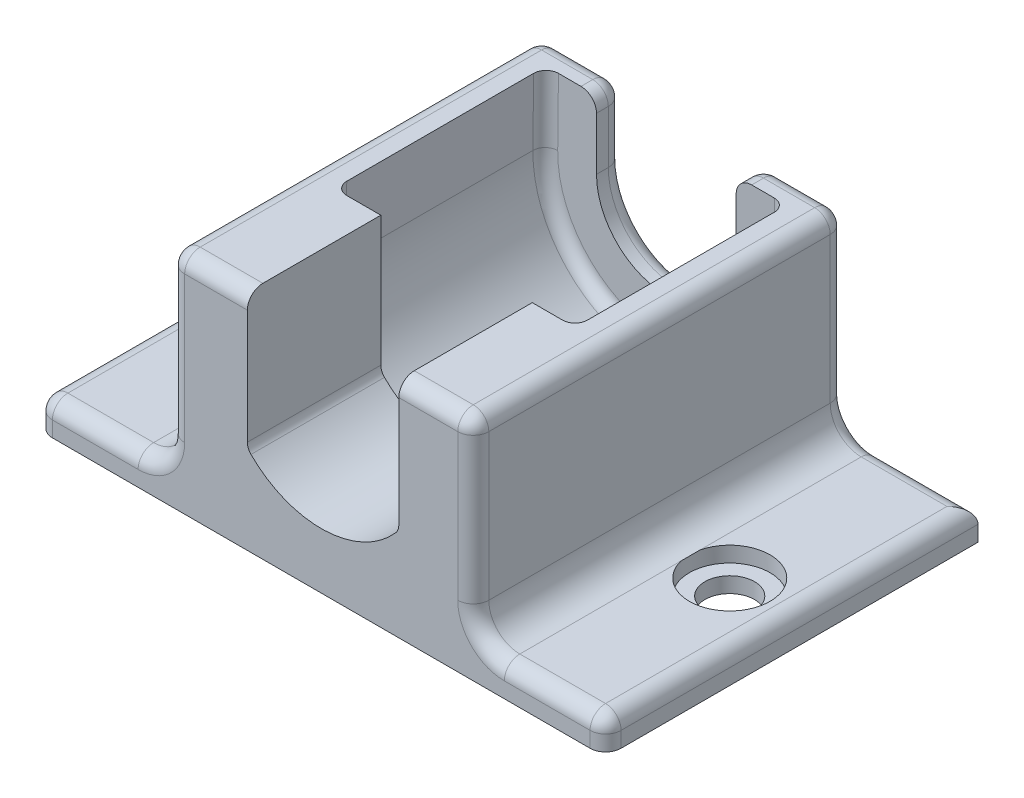
SolidWorks part; units mm, degrees
ref_plane "Front Plane" through (0, 0, 0) normal (0, 0, 1) x (1, 0, 0)
ref_plane "Top Plane" through (0, 0, 0) normal (0, 1, 0) x (1, 0, 0)
ref_plane "Right Plane" through (0, 0, 0) normal (1, 0, 0) x (0, 0, -1)
sketch "Sketch1" plane through (0, 0, 0) normal (0, 0, 1) x (1, 0, 0)
  line L6 (-23.375, 0) -> (-18.375, 0)
  line L7 (18.375, 0) -> (23.375, 0)
  arc A2 (-18.375, 0) -> (18.375, 0) centre (0, 0) ccw
  arc A3 (-23.375, 0) -> (23.375, 0) centre (0, 0) ccw
  dimension "D1" = 18.375
  dimension "D2" = 23.375
extrude "Boss-Extrude1" add sketch "Sketch1" along normal blind 18.5 contours L6 A3 L7 A2
sketch "Sketch2" plane through (0, 0, 18.5) normal (0, 0, 1) x (1, 0, 0)
  line L0 (-16.375, 0) -> (-23.375, 0)
  line L1 (16.375, 0) -> (23.375, 0)
  arc A0 (-23.375, 0) -> (23.375, 0) centre (0, 0) ccw
  arc A1 (-16.375, 0) -> (16.375, 0) centre (0, 0) ccw
  dimension "D1" = 32.75
  dimension "D2" = 46.75
extrude "Boss-Extrude2" add sketch "Sketch2" along normal blind 18
sketch "Sketch3" plane through (0, 0, 0) normal (0, 0, -1) x (-1, 0, 0)
  line L0 (-23.375, 0) -> (23.375, 0)
  arc A0 (-23.375, 0) -> (23.375, 0) centre (0, 0) ccw
  circle A1 centre (0, -7) radius 6.5
  dimension "D2" = 13
  dimension "D1" = 7
extrude "Boss-Extrude3" add sketch "Sketch3" along normal blind 5
sketch "Sketch4" plane through (0, 0, 0) normal (0, 1, 0) x (1, 0, 0)
  line L0 (23.375, -36.5) -> (23.375, 5)
  line L1 (23.375, 5) -> (-23.375, 5)
  line L2 (-23.375, 5) -> (-23.375, -36.5)
  line L3 (-23.375, -36.5) -> (-16.375, -36.5)
  line L4 (-16.375, -36.5) -> (-16.375, -18.5)
  line L5 (-16.375, -18.5) -> (-18.375, -18.5)
  line L6 (-18.375, -18.5) -> (-18.375, 0)
  line L7 (-18.375, 0) -> (18.375, 0)
  line L8 (18.375, 0) -> (18.375, -18.5)
  line L9 (18.375, -18.5) -> (16.375, -18.5)
  line L10 (16.375, -18.5) -> (16.375, -36.5)
  line L11 (16.375, -36.5) -> (23.375, -36.5)
extrude "Boss-Extrude4" add sketch "Sketch4" along normal blind 5
sketch "Sketch5" plane through (0, 0, -5) normal (0, 0, -1) x (-1, 0, 0)
  line L0 (-6.5, -7) -> (-6.5, 5)
  line L1 (-23.375, 5) -> (23.375, 5) construction
  line L2 (-6.5, 5) -> (6.5, 5)
  line L3 (6.5, 5) -> (6.5, -7)
  line L4 (-6.5, -7) -> (6.5, -7)
  circle A0 centre (0, -7) radius 6.5 construction
  circle A1 centre (0, -7) radius 6.5 construction
extrude "Cut-Extrude1" cut sketch "Sketch5" against normal blind 5
ref_plane "Plane1" through (0, -54, 0) normal (0, 1, 0) x (1, 0, 0)
sketch "Sketch6" plane through (0, -54, 0) normal (0, 1, 0) x (1, 0, 0)
  line L0 (23.375, -36.5) -> (23.375, 5) construction
  line L1 (13.215, 5) -> (23.375, 5)
  line L2 (13.215, 5) -> (13.215, -36.5)
  line L3 (13.215, -36.5) -> (23.375, -36.5)
  line L4 (23.375, 5) -> (23.375, -36.5)
  line L6 (-13.215, 5) -> (-23.375, 5)
  line L7 (-13.215, 5) -> (-13.215, -36.5)
  line L8 (-13.215, -36.5) -> (-23.375, -36.5)
  line L9 (-23.375, 5) -> (-23.375, -36.5)
  line L10 (-23.375, 5) -> (-23.375, -36.5) construction
  line L11 (-23.375, -36.5) -> (-16.375, -36.5) construction
  line L12 (16.375, -36.5) -> (23.375, -36.5) construction
  line L13 (-6.5, 5) -> (-23.375, 5) construction
  line L14 (23.375, 5) -> (6.5, 5) construction
  line L15 (6.5, 5) -> (-6.5, 5) construction
  line L16 (-3.175, 5) -> (3.175, 5)
  line L17 (-3.175, 5) -> (-3.175, -36.5)
  line L18 (-3.175, -36.5) -> (3.175, -36.5)
  line L19 (3.175, 5) -> (3.175, -36.5)
  line L20 (-16.375, -36.5) -> (16.375, -36.5) construction
  dimension "D1" = 6.35
  dimension "D2" = 3.175
  dimension "D3" = 10.16
  dimension "D4" = 0
  dimension "D5" = 10.16
  dimension "D7" = 0
extrude "Boss-Extrude5" add sketch "Sketch6" along normal up to next
sketch "Sketch7" plane through (0, -54, 0) normal (0, -1, 0) x (1, 0, 0)
  line L0 (-13.215, -5) -> (-23.375, -5) construction
  line L1 (-23.375, 36.5) -> (37.5, 36.5)
  line L2 (-23.375, 36.5) -> (-23.375, -5)
  line L3 (-23.375, -5) -> (37.5, -5)
  line L4 (37.5, 36.5) -> (37.5, -5)
  line L5 (-23.375, 36.5) -> (-13.215, 36.5) construction
  line L7 (-23.375, -5) -> (-23.375, 36.5) construction
  dimension "D1" = 0
  dimension "D2" = 0
  dimension "D4" = 37.5
extrude "Boss-Extrude6" add sketch "Sketch7" against normal blind 5
sketch "Sketch10" plane through (23.375, 0, 0) normal (1, 0, 0) x (0, 0, -1)
  line L0 (5, -49) -> (-36.5, -49) construction
  line L1 (-31.7375, -23.1584) -> (0.2375, -23.1584)
  line L2 (-31.7375, -23.1584) -> (-31.7375, -46)
  line L3 (-31.7375, -46) -> (0.2375, -46)
  line L4 (0.2375, -23.1584) -> (0.2375, -46)
  line L5 (5, 5) -> (5, -49) construction
  line L6 (-36.5, 5) -> (-36.5, -49) construction
  line L7 (-36.5, -23.1584) -> (5, -23.1584) construction
  dimension "D1" = 3
  dimension "D2" = 4.7625
  dimension "D3" = 4.7625
  dimension "D4" = 0
extrude "Cut-Extrude2" cut sketch "Sketch10" against normal through all
sketch "Sketch12" plane through (0, 0, -5) normal (0, 0, -1) x (-1, 0, 0)
  line L0 (-23.375, 0) -> (-23.375, 5)
  line L1 (-23.375, 5) -> (-12.2555, 5)
  line L2 (23.375, 5) -> (23.375, 0)
  line L3 (-12.2555, -7) -> (-12.2555, 5)
  line L4 (12.2555, -7) -> (12.2555, 5)
  line L5 (12.2555, 5) -> (23.375, 5)
  arc A0 (-23.375, 0) -> (23.375, 0) centre (0, 0) ccw
  arc A1 (-12.2555, -7) -> (12.2555, -7) centre (0, -7) ccw
  dimension "D1" = 24.511
extrude "Boss-Extrude7" add sketch "Sketch12" against normal through all contours A1 L4 L5 L2 A0 L0 L1 L3
sketch "Sketch13" plane through (0, 0, -5) normal (0, 0, -1) x (-1, 0, 0)
  line L1 (-12.3818, -6.8682) -> (-12.2555, 5)
  line L2 (-12.2555, 5) -> (12.2555, 5)
  line L3 (12.2555, 5) -> (12.3818, -6.8682)
  arc A0 (-12.3818, -6.8682) -> (12.3818, -6.8682) centre (0, -7) ccw
  dimension "D1" = 24.765
extrude "Cut-Extrude4" cut sketch "Sketch13" against normal through all
ref_plane "Plane2" through (0, 0, 19.4475) normal (0, 0, -1) x (-1, 0, 0)
sketch "Sketch14" plane through (0, 0, 19.4475) normal (0, 0, -1) x (-1, 0, 0)
  line L0 (-7.9375, -0.6579) -> (-7.9375, -13.3421)
  line L1 (7.5565, -13.7915) -> (7.5565, -1.1074)
  line L2 (-7.9375, -0.6579) -> (-7.9375, 5)
  line L3 (-7.9375, 5) -> (-23.375, 5)
  line L4 (-23.375, 5) -> (-23.375, 0)
  line L6 (7.5565, -1.1074) -> (7.5565, 5)
  line L7 (7.5565, 5) -> (23.375, 5)
  line L8 (23.375, 5) -> (23.375, 0)
  arc A0 (-7.9375, -13.3421) -> (7.5565, -13.7915) centre (0, -7) ccw
  arc A1 (-23.375, 0) -> (23.375, 0) centre (0, 0) ccw
  arc A2 (-12.3818, -6.8682) -> (12.3818, -6.8682) centre (0, -7) ccw construction
  dimension "D1" = 20.32
  dimension "D3" = 23.375
  dimension "D2" = 15.494
extrude "Boss-Extrude8" add sketch "Sketch14" against normal through all
sketch "Sketch15" plane through (0, 0, -5) normal (0, 0, -1) x (-1, 0, 0)
  line L0 (-6.0325, -7) -> (-6.0325, 5)
  line L1 (-6.0325, 5) -> (-12.3825, 5)
  line L2 (-12.3825, 5) -> (-12.3825, -7)
  line L3 (6.0325, -7) -> (6.0325, 5)
  line L4 (6.0325, 5) -> (12.3825, 5)
  line L6 (12.3825, 5) -> (12.3825, -7)
  line L7 (12.2555, 5) -> (7.5565, 5) construction
  line L8 (-7.9375, 5) -> (-12.2555, 5) construction
  arc A0 (-6.0325, -7) -> (6.0325, -7) centre (0, -7) ccw
  arc A2 (-12.3825, -7) -> (12.3825, -7) centre (0, -7) ccw
extrude "Boss-Extrude9" add sketch "Sketch15" against normal blind 2.794
sketch "Sketch16" plane through (0, 5, 0) normal (0, 1, 0) x (1, 0, 0)
  line L1 (33.3775, -19.1282) -> (33.3725, -12.7782)
  line L2 (37.5, 5) -> (37.5, -36.5) construction
  line L3 (28.9275, -19.13) -> (28.9275, -12.78)
  line L4 (23.375, 5) -> (37.5, 5) construction
  arc A0 (33.3725, -12.7782) -> (28.9275, -12.78) centre (31.15, -12.78) ccw
  arc A1 (28.9275, -19.13) -> (33.3775, -19.1282) centre (31.1525, -19.13) ccw
  point P4 (31.15, -15.955)
  dimension "D7" = 2.2225
  dimension "D1" = 3.175
  dimension "D2" = 4.45
  dimension "D3" = 6.35
  dimension "D4" = 2.2225
  dimension "D5" = 6.35
  dimension "D6" = 20.955
extrude "Cut-Extrude5" cut sketch "Sketch16" against normal through all contours A0 | A0 | A1 L1 A0 L3 | A1 | A1 region at (31.1513, 5, 15.9572)
sketch "Sketch19" plane through (37.5, 0, 0) normal (1, 0, 0) x (0, 0, -1)
  line L1 (-36.5, -49) -> (5, -49)
  line L2 (-36.5, -49) -> (-36.5, -54)
  line L3 (-36.5, -54) -> (5, -54)
  line L4 (5, -49) -> (5, -54)
extrude "Boss-Extrude10" add sketch "Sketch19" along normal blind 3.175
sketch "Sketch18" plane through (0, -49, 0) normal (0, 1, 0) x (1, 0, 0)
  line L28 (27.025, -12.7816) -> (27.0275, -19.1316)
  line L29 (35.2775, -19.1284) -> (35.275, -12.7784)
  arc A22 (33.3725, -12.7782) -> (28.9275, -12.78) centre (31.15, -12.78) ccw construction
  arc A23 (28.9275, -19.13) -> (33.3775, -19.1282) centre (31.1525, -19.13) ccw construction
  arc A26 (35.275, -12.7784) -> (27.025, -12.7816) centre (31.15, -12.78) ccw
  arc A29 (27.0275, -19.1316) -> (35.2775, -19.1284) centre (31.1525, -19.13) ccw
  dimension "D1" = 4.125
  dimension "D2" = 4.125
extrude "Cut-Extrude6" cut sketch "Sketch18" against normal blind 1.5 and the other way through all contours L29 A26 L28 A29
fillet "Fillet1" radius 1.27 8 edges at (-7.5565, -13.7915, 27.9738) (7.9375, -13.3421, 27.9738) (-12.3186, -0.9341, -2.206) (0, -19.3825, -2.206) (12.3186, -0.9341, 19.4475) (0, -19.3825, 19.4475) (12.3186, -0.9341, -2.206) (-12.3186, -0.9341, 19.4475)
fillet "Fillet3" radius 3.175 4 edges at (3.175, -23.1584, 34.1187) (-3.175, -23.1584, -2.6188) (3.175, -23.1584, -2.6188) (-3.175, -23.1584, 34.1187)
fillet "Fillet4" radius 9.525 12 edges at (0, -46, 31.7375) (-18.295, -46, 31.7375) (-18.295, -46, -0.2375) (0, -46, -0.2375) (-18.295, -23.1584, -0.2375) (-18.295, -23.1584, 31.7375) (18.295, -23.1584, -0.2375) (18.295, -46, -0.2375) (18.295, -46, 31.7375) (18.295, -23.1584, 31.7375) (0, -23.375, -0.2375) (0, -23.375, 31.7375)
sketch "Sketch20" plane through (0, 0, -5) normal (0, 0, -1) x (-1, 0, 0)
  line L0 (23.375, 5) -> (23.375, -54) construction
  line L1 (-23.375, 5) -> (23.375, 5)
  line L2 (-23.375, 5) -> (-23.375, 0)
  line L3 (-23.375, 0) -> (23.375, 0)
  line L4 (23.375, 5) -> (23.375, 0)
extrude "Cut-Extrude7" cut sketch "Sketch20" against normal through all
sketch "Sketch21" plane through (0, 0, 36.5) normal (0, 0, 1) x (1, 0, 0)
  line L0 (-23.375, -54) -> (40.675, -54) construction
  line L1 (-23.375, 0) -> (-19.565, 0)
  line L2 (-23.375, 0) -> (-23.375, -54)
  line L3 (-23.375, -54) -> (-19.565, -54)
  line L4 (-19.565, 0) -> (-19.565, -54)
  line L6 (23.375, 0) -> (19.565, 0)
  line L7 (23.375, 0) -> (23.375, -49)
  line L8 (23.375, -49) -> (19.565, -49)
  line L9 (19.565, 0) -> (19.565, -49)
  line L10 (40.675, -49) -> (23.375, -49) construction
  line L12 (40.675, -49) -> (37.5, -49)
  line L13 (40.675, -49) -> (40.675, -54)
  line L14 (40.675, -54) -> (37.5, -54)
  line L15 (37.5, -49) -> (37.5, -54)
  dimension "D1" = 3.81
  dimension "D2" = 3.81
  dimension "D3" = 3.175
extrude "Cut-Extrude8" cut sketch "Sketch21" against normal through all
sketch "Sketch22" plane through (0, 0, -5) normal (0, 0, -1) x (-1, 0, 0)
  line L0 (-19.565, 0) -> (-19.565, -49) construction
  line L1 (19.565, -54) -> (-19.565, -54)
  line L2 (19.565, -54) -> (19.565, -19.2809)
  line L3 (19.565, -19.2809) -> (13.215, -19.2809)
  line L4 (-19.565, -54) -> (-19.565, -19.2809)
  line L5 (-13.215, -19.2809) -> (-19.565, -19.2809)
  arc A0 (-13.215, -19.2809) -> (13.215, -19.2809) centre (0, 0) ccw
  arc A1 (-13.215, -19.2809) -> (-5.5906, -22.6966) centre (0, 0) ccw construction
extrude "Boss-Extrude11" add sketch "Sketch22" against normal through all
sketch "Sketch24" plane through (0, 0, -5) normal (0, 0, -1) x (-1, 0, 0)
  line L0 (19.565, -54) -> (19.565, 0) construction
  line L1 (-37.5, -54) -> (19.565, -54)
  line L2 (-37.5, -54) -> (-37.5, -22.875)
  line L3 (-37.5, -22.875) -> (19.565, -22.875)
  line L4 (19.565, -54) -> (19.565, -22.875)
  arc A0 (-6.0325, -7) -> (6.0325, -7) centre (0, -7) ccw construction
  dimension "D1" = 15.875
extrude "Cut-Extrude9" cut sketch "Sketch24" against normal through all
sketch "Sketch25" plane through (0, 0, 36.5) normal (0, 0, 1) x (1, 0, 0)
  line L1 (-19.565, -22.875) -> (-29.09, -22.875)
  line L2 (-19.565, -22.875) -> (-19.565, -19.7)
  line L3 (-19.565, -19.7) -> (-29.09, -19.7)
  line L4 (-29.09, -22.875) -> (-29.09, -19.7)
  line L5 (19.565, -22.875) -> (29.09, -22.875)
  line L6 (19.565, -22.875) -> (19.565, -19.7)
  line L7 (19.565, -19.7) -> (29.09, -19.7)
  line L8 (29.09, -22.875) -> (29.09, -19.7)
  dimension "D1" = 3.175
  dimension "D2" = 3.175
  dimension "D3" = 9.525
  dimension "D4" = 9.525
extrude "Boss-Extrude12" add sketch "Sketch25" against normal through all
sketch "Sketch26" plane through (0, 0, 0) normal (0, 1, 0) x (1, 0, 0)
  line L0 (-6.0325, 5) -> (-19.565, 5) construction
  line L1 (-15.5568, 5) -> (15.5568, 5)
  line L2 (-15.5568, 5) -> (-15.5568, -36.5)
  line L3 (-15.5568, -36.5) -> (15.5568, -36.5)
  line L4 (15.5568, 5) -> (15.5568, -36.5)
  line L5 (19.565, -36.5) -> (7.9375, -36.5) construction
  line L6 (12.3818, -18.1775) -> (12.3818, 0.936) construction
  line L7 (-12.3818, -18.1775) -> (-12.3818, 0.936) construction
  line L9 (-19.565, 5) -> (19.565, 5)
  line L10 (-19.565, 5) -> (-19.565, -36.5)
  line L11 (-19.565, -36.5) -> (19.565, -36.5)
  line L12 (19.565, 5) -> (19.565, -36.5)
  line M1 (-6.0325, 5) -> (-19.565, 5)
  line M2 (-19.565, 5) -> (-19.565, -36.5)
  line M3 (-19.565, -36.5) -> (-7.5565, -36.5)
  dimension "D1" = 3.175
  dimension "D2" = 3.175
extrude "Cut-Extrude10" cut sketch "Sketch26" against normal up to surface (19.7 mm away) contours L2 M1 M2 M3 | L12 L9 L4 L11 region at (-17.5609, 0, 15.75) region at (17.5609, 0, 15.75) up to face at (-21.9462, -19.7, 10.5625)
fillet "Fillet5" radius 3.175 2 edges at (15.5568, -19.7, 15.75) (-15.5568, -19.7, 15.75)
fillet "Fillet6" radius 1.5875 20 edges at (16.4867, -18.7701, -5) (-16.4867, -18.7701, -5) (16.4867, -18.7701, 36.5) (-16.4867, -18.7701, 36.5) (-10.7946, 0, -5) (10.7946, 0, -5) (15.5568, -8.2625, -5) (-15.5568, -8.2625, -5) (29.09, -19.7, 15.75) (-29.09, -19.7, 15.75) (15.5568, -8.2625, 36.5) (-15.5568, -8.2625, 36.5) (11.7471, 0, 36.5) (-11.5566, 0, 36.5) (15.5568, 0, 15.75) (-15.5568, 0, 15.75)
hole_wizard "Hole1" positions "Sketch28" profile "Sketch27" legacy end condition through all
sketch "Sketch28" plane through (0, -19.7, 0) normal (0, 1, 0) x (1, 0, 0)
  line L0 (-29.09, 5) -> (-18.7318, 5) construction
  line L1 (18.7318, 5) -> (29.09, 5) construction
  line L2 (29.09, 5) -> (29.09, -36.5) construction
  line L3 (-29.09, -36.5) -> (-29.09, 5) construction
  point P0 (-22.74, -14.05)
  point P2 (22.74, -14.05)
  dimension "D1" = 19.05
  dimension "D2" = 19.05
  dimension "D3" = 6.35
  dimension "D4" = 6.35
sketch "Sketch27" plane through (-22.74, -19.7, 14.05) normal (1, 0, 0) x (0, 0, 1)
  line L0 (0, 0) -> (0, 3.175)
  line L1 (0, 3.175) -> (2.54, 3.175)
  line L3 (2.54, 3.175) -> (2.54, 1.5875)
  line L4 (2.54, 1.5875) -> (4.1275, 1.5875)
  line L5 (4.1275, 1.5875) -> (4.1275, 0)
  line L7 (4.1275, 0) -> (0, 0)
  line L11 (0, -6.35) -> (0, 107.95) construction
  dimension "Thru Hole Dia." = 5.08
  dimension "Thru Hole Depth" = 3.175
  dimension "C'Bore Dia." = 8.255
  dimension "C'Bore Depth" = 1.5875
sketch "Sketch29" plane through (0, -22.875, 0) normal (0, -1, 0) x (1, 0, 0)
  line L0 (29.09, -5) -> (29.09, 36.5) construction
  line L1 (-29.09, 36.5) -> (29.09, 36.5)
  line L2 (-29.09, 36.5) -> (-29.09, 33.1)
  line L3 (-29.09, 33.1) -> (29.09, 33.1)
  line L4 (29.09, 36.5) -> (29.09, 33.1)
  line L5 (-29.09, -5) -> (29.09, -5) construction
  dimension "D1" = 38.1
extrude "Cut-Extrude11" cut sketch "Sketch29" against normal through all contours L1 L4 L3 L2
sketch "Sketch30" plane through (0, 0, -5) normal (0, 0, -1) x (-1, 0, 0)
  line L0 (-7.1438, -7) -> (-7.1438, 0)
  line L1 (-13.9693, 0) -> (-6.0325, 0) construction
  line L2 (-7.1438, 0) -> (7.1437, 0)
  line L3 (6.0325, 0) -> (13.9693, 0) construction
  line L4 (7.1437, 0) -> (7.1438, -7)
  circle A0 centre (0, -7) radius 7.1438
  arc A1 (-6.0325, -7) -> (6.0325, -7) centre (0, -7) ccw construction
  line M9 (13.9693, -1.5875) -> (6.0325, -1.5875)
  line M10 (6.0325, -1.5875) -> (6.0325, -7)
  arc M11 (6.0325, -7) -> (-6.0325, -7) centre (0, -7) cw
  line M12 (-6.0325, -7) -> (-6.0325, -1.5875)
  line M13 (-6.0325, -1.5875) -> (-13.9693, -1.5875)
  dimension "D1" = 14.2875
extrude "Cut-Extrude12" cut sketch "Sketch30" against normal blind 3.175 contours A0 L2 L0 M13 M12 | A0 L2 M10 M12 M11 | A0 L4 L2 M10 M9 | A0 L4 M9 M10 | A0 L0 M12 M13 | A0 M10 M11 M12 region at (6.6873, -5.0579, -5) region at (6.6875, -3.139, -5) region at (5.2268, -0.8853, -5) region at (-6.6875, -3.139, -5) region at (0, -6.3419, -5) region at (-5.2268, -0.8853, -5)
fillet "Fillet7" radius 1.5875 21 edges at (10.9534, 0, 33.1) (15.0918, -0.465, 33.1) (29.09, -22.0812, 33.1) (28.625, -20.165, 33.1) (23.1171, -19.7, 33.1) (16.4867, -18.7701, 33.1) (-10.7629, 0, 33.1) (-15.0918, -0.465, 33.1) (-29.09, -22.0812, 33.1) (-28.625, -20.165, 33.1) (-23.1171, -19.7, 33.1) (-16.4867, -18.7701, 33.1) (7.1438, 0, -2.8092) (7.1438, -0.465, -4.535) (7.1438, -4.2938, -5) (-7.1438, 0, -2.8092) (-7.1438, -0.465, -4.535) (-7.1438, -4.2938, -5) (15.5568, -9.0562, 33.1) (-15.5568, -9.0562, 33.1) (0, -14.1438, -5)
